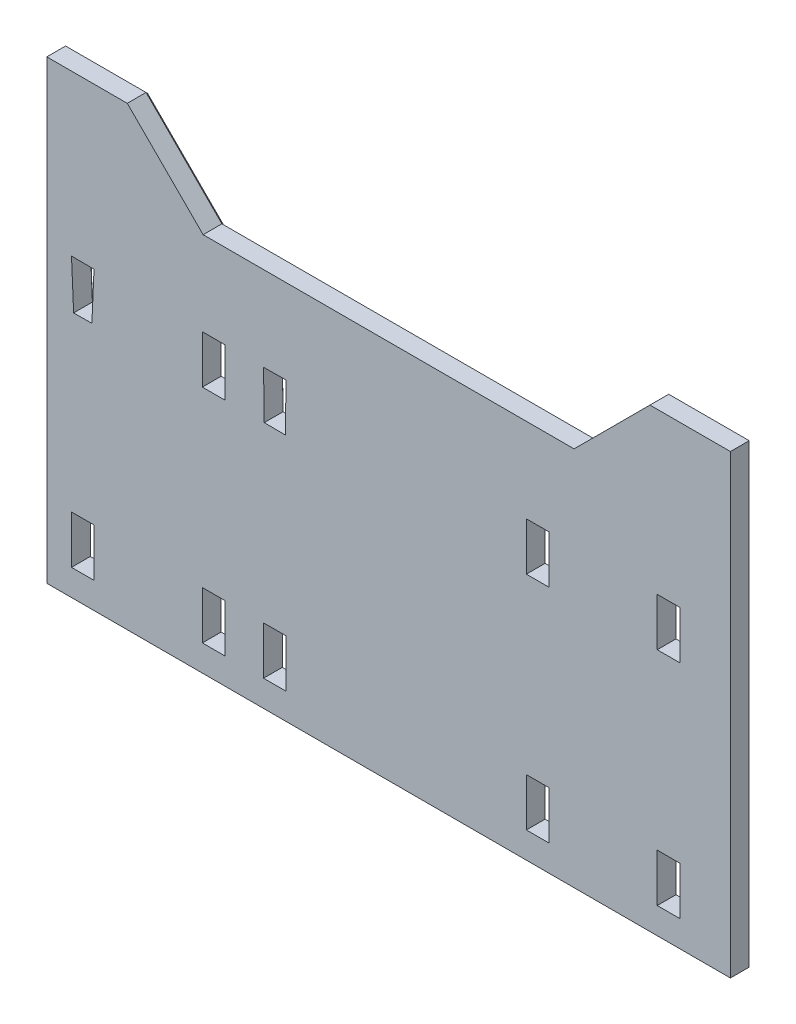
SolidWorks part; units mm, degrees
ref_plane "Front Plane" through (0, 0, 0) normal (0, 0, 1) x (1, 0, 0)
ref_plane "Top Plane" through (0, 0, 0) normal (0, 1, 0) x (1, 0, 0)
ref_plane "Right Plane" through (0, 0, 0) normal (1, 0, 0) x (0, 0, -1)
sketch "Sketch1" plane through (0, 0, 0) normal (0, 0, 1) x (1, 0, 0)
  line L6 (-34.7201, 25.1212) -> (-30.5201, 25.1212)
  line L7 (25.6799, 25.1212) -> (29.8799, 25.1212)
  line L8 (25.6799, 25.1212) -> (25.6799, 16.1788)
  line L9 (25.6799, 16.1788) -> (29.8799, 16.1788)
  line L10 (29.8799, 25.1212) -> (29.8799, 16.1788)
  line L12 (25.6799, -16.1788) -> (29.8799, -16.1788)
  line L13 (25.6799, -25.1212) -> (25.6799, -16.1788)
  line L14 (29.8799, -25.1212) -> (29.8799, -16.1788)
  line L15 (25.6799, -25.1212) -> (29.8799, -25.1212)
  line L16 (-19.1202, 25.1207) -> (-23.32, 25.0887)
  line L17 (-19.1202, 25.1207) -> (-19.2553, 16.1793)
  line L18 (-23.32, 25.0887) -> (-23.1849, 16.2113)
  line L19 (-19.2553, 16.1793) -> (-23.1849, 16.2113)
  line L20 (-19.1201, -16.1788) -> (-23.3201, -16.1788)
  line L21 (-19.1201, -25.1212) -> (-19.1201, -16.1788)
  line L22 (-23.3201, -25.1212) -> (-23.3201, -16.1788)
  line L23 (-19.1201, -25.1212) -> (-23.3201, -25.1212)
  line L39 (50.0799, 25.1212) -> (54.2799, 25.1212)
  line L40 (50.0799, 25.1212) -> (50.0799, 16.1788)
  line L41 (50.0799, 16.1788) -> (54.2799, 16.1788)
  line L42 (54.2799, 25.1212) -> (54.2799, 16.1788)
  line L43 (50.0799, -16.1788) -> (54.2799, -16.1788)
  line L44 (50.0799, -16.1788) -> (50.0799, -25.1212)
  line L45 (50.0799, -25.1212) -> (54.2799, -25.1212)
  line L46 (54.2799, -16.1788) -> (54.2799, -25.1212)
  line L47 (-34.7201, 25.1212) -> (-34.7201, 16.1788)
  line L48 (-34.7201, 16.1788) -> (-30.5201, 16.1788)
  line L49 (-30.5201, 25.1212) -> (-30.5201, 16.1788)
  line L50 (-34.7201, -16.1788) -> (-30.5201, -16.1788)
  line L51 (-34.7201, -16.1788) -> (-34.7201, -25.1212)
  line L52 (-34.7201, -25.1212) -> (-30.5201, -25.1212)
  line L53 (-30.5201, -16.1788) -> (-30.5201, -25.1212)
  line L60 (-59.12, 25.1456) -> (-54.9201, 25.1168)
  line L61 (-59.12, 25.1456) -> (-58.7228, 16.1544)
  line L62 (-58.7228, 16.1544) -> (-55.3174, 16.1832)
  line L63 (-54.9201, 25.1168) -> (-55.3174, 16.1832)
  line L64 (-59.1201, -16.1788) -> (-54.9201, -16.1788)
  line L65 (-59.1201, -16.1788) -> (-59.1201, -25.1212)
  line L66 (-59.1201, -25.1212) -> (-54.9201, -25.1212)
  line L67 (-54.9201, -16.1788) -> (-54.9201, -25.1212)
  line L80 (-63.7201, 30) -> (63.7201, 30)
  line L81 (63.7201, 30) -> (63.7201, -30)
  line L82 (52.1799, 25.1212) -> (52.1799, 16.1788) construction
  line L83 (27.7799, 16.1788) -> (27.7799, 25.1212) construction
  line L84 (-63.7201, 30) -> (-63.7201, -30)
  line L85 (-63.7201, -30) -> (63.7201, -30)
  line L87 (53.2799, 20.65) -> (50.0799, 20.65) construction
  line L88 (29.8799, 20.65) -> (25.6799, 20.65) construction
  line L89 (54.2799, -20.65) -> (50.0799, -20.65) construction
  line L90 (52.1799, -16.1788) -> (52.1799, -25.1212) construction
  line L91 (27.7799, -16.1788) -> (27.7799, -25.1212) construction
  line L92 (29.8799, -20.65) -> (25.6799, -20.65) construction
  line L93 (-19.1201, -20.65) -> (-23.3201, -20.65) construction
  line L94 (-21.2201, -16.1788) -> (-21.2201, -25.1212) construction
  line L95 (-32.6201, -16.1788) -> (-32.6201, -25.1212) construction
  line L96 (-30.5201, -20.65) -> (-34.7201, -20.65) construction
  line L97 (-54.9201, -20.65) -> (-59.1201, -20.65) construction
  line L98 (-57.0201, -16.1788) -> (-57.0201, -25.1212) construction
  line L99 (-57.0201, 25.1312) -> (-57.0201, 16.1688) construction
  line L100 (-32.6201, 25.1212) -> (-32.6201, 16.1788) construction
  line L101 (-21.2201, 25.1047) -> (-21.2201, 16.1953) construction
  line L102 (-55.1188, 20.65) -> (-58.9214, 20.65) construction
  line L103 (-34.7201, 20.65) -> (-30.5201, 20.65) construction
  line L104 (-19.1877, 20.65) -> (-23.2525, 20.65) construction
  point P0 (0, 0)
  point P86 (0, 30)
  point P87 (63.7201, 0)
  dimension "D1" = 9
  dimension "D2" = 4.2
  dimension "D3" = 127.4402
  dimension "D4" = 60
  dimension "D7" = 11.4
  dimension "D8" = 24.4
  dimension "D5" = 27.7799
  dimension "D6" = 21.2201
  dimension "D10" = 20.65
  dimension "D11" = 20.65
  dimension "D9" = 24.4
extrude "Boss-Extrude1" add sketch "Sketch1" against normal blind 4
sketch "Sketch2" plane through (0, 0, 0) normal (0, 0, 1) x (1, 0, 0)
  line L0 (-63.7201, 30) -> (-63.7201, 55)
  line L1 (-63.7201, 55) -> (-48.7201, 55)
  line L2 (-48.7201, 55) -> (-34.578, 40.8579)
  line L7 (63.7201, 30) -> (-63.7201, 30)
  line L8 (48.7201, 55) -> (63.7201, 55)
  line L9 (63.7201, 55) -> (63.7201, 30)
  line L10 (48.7201, 55) -> (34.578, 40.8579)
  line L11 (34.578, 40.8579) -> (-34.578, 40.8579)
  line L12 (-63.7201, 30) -> (-63.7201, -30) construction
  line L14 (63.7201, -30) -> (63.7201, 30) construction
  dimension "D1" = 25
  dimension "D2" = 15
  dimension "D3" = 135
  dimension "D4" = 20
extrude "Boss-Extrude2" add sketch "Sketch2" against normal blind 4
chamfer "Chamfer1" distance 0.5 angle 45 48 edges at (56.2201, 55, -4) (41.649, 47.9289, -4) (0, 40.8579, -4) (-41.649, 47.9289, -4) (-56.2201, 55, -4) (-63.7201, 12.5, -4) (0, -30, -4) (63.7201, 12.5, -4) (29.8799, 20.65, -4) (27.7799, 16.1788, -4) (25.6799, 20.65, -4) (27.7799, 25.1212, -4) (29.8799, -20.65, -4) (27.7799, -25.1212, -4) (25.6799, -20.65, -4) (27.7799, -16.1788, -4) (-23.2525, 20.65, -4) (-21.2201, 25.1047, -4) (-19.1877, 20.65, -4) (-21.2201, 16.1953, -4) (-23.3201, -20.65, -4) (-21.2201, -16.1788, -4) (-19.1201, -20.65, -4) (-21.2201, -25.1212, -4) (-30.5201, 20.65, -4) (-32.6201, 16.1788, -4) (-34.7201, 20.65, -4) (-32.6201, 25.1212, -4) (-30.5201, -20.65, -4) (-32.6201, -25.1212, -4) (-34.7201, -20.65, -4) (-32.6201, -16.1788, -4) (54.2799, 20.65, -4) (52.1799, 16.1788, -4) (50.0799, 20.65, -4) (52.1799, 25.1212, -4) (54.2799, -20.65, -4) (52.1799, -25.1212, -4) (50.0799, -20.65, -4) (52.1799, -16.1788, -4) (-55.1188, 20.65, -4) (-57.0201, 16.1688, -4) (-58.9214, 20.65, -4) (-57.0201, 25.1312, -4) (-54.9201, -20.65, -4) (-57.0201, -25.1212, -4) (-59.1201, -20.65, -4) (-57.0201, -16.1788, -4)
equation "\"pin_hole_height\"=9"
equation "\"D1@Sketch1\"=\"pin_hole_height\""
equation "\"pin_hole_width\"=4.2"
equation "\"D2@Sketch1\"=\"pin_hole_width\""
